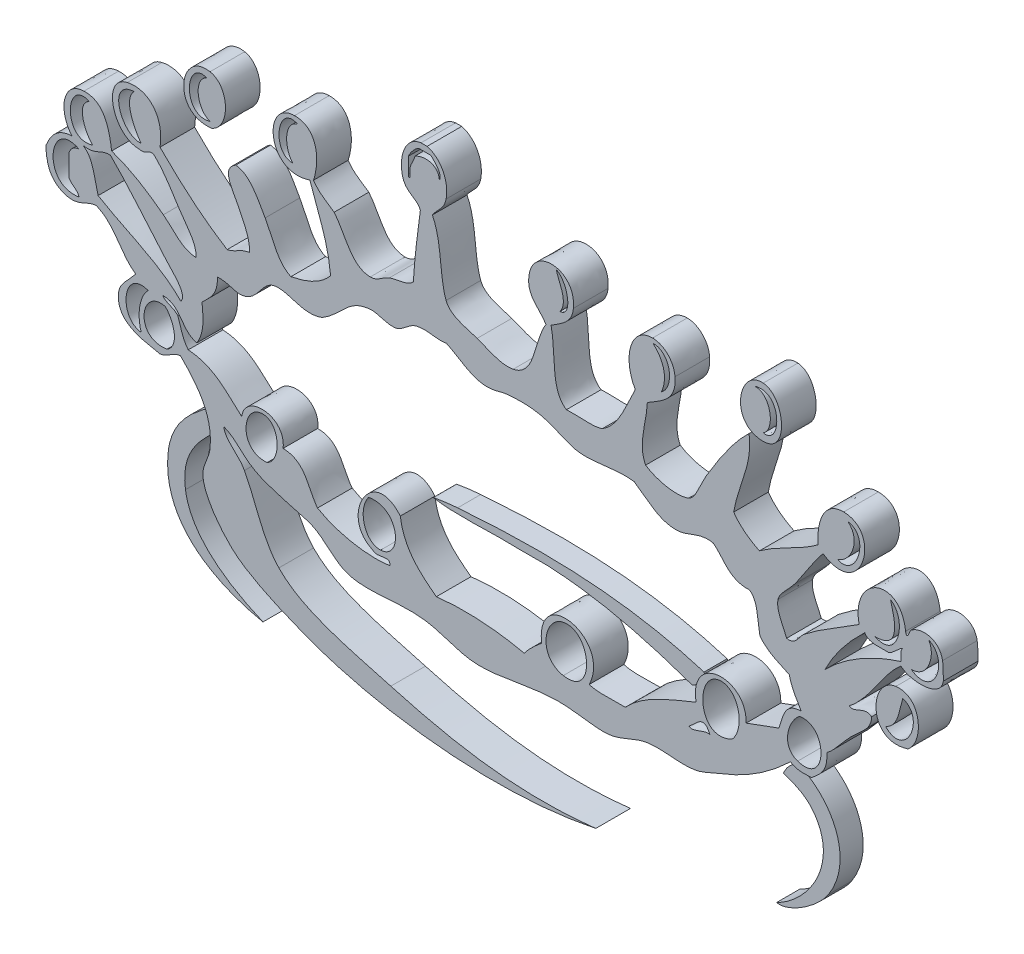
SolidWorks part; units mm, degrees
ref_plane "Front Plane" through (0, 0, 0) normal (0, 0, 1) x (1, 0, 0)
ref_plane "Top Plane" through (0, 0, 0) normal (0, 1, 0) x (1, 0, 0)
ref_plane "Right Plane" through (0, 0, 0) normal (1, 0, 0) x (0, 0, -1)
sketch "Sketch1" plane through (0, 0, 0) normal (0, 0, 1) x (1, 0, 0)
  line L1 (0, 0) -> (155.4725, 0) construction
  line L2 (0, 0) -> (0, 91.1172) construction
  line L3 (0, 91.1172) -> (155.4725, 91.1172) construction
  line L4 (155.4725, 0) -> (155.4725, 91.1172) construction
  point P5 (0, 0)
  point P6 (0, 0)
  spline B0 degree 3 poles (112.0338, 34.261) (112.3994, 33.3103) (111.1196, 31.738) (109.9496, 31.2992) knots 5 5 5 5 6 6 6 6
  spline B1 degree 3 poles (69.3629, 37.5518) (85.2319, 38.7584) (98.7608, 38.3196) (112.0338, 34.261) knots 4 4 4 4 5 5 5 5
  spline B2 degree 3 poles (65.1946, 36.9668) (64.6461, 37.0764) (69.1435, 37.5518) (69.3629, 37.5518) knots 3 3 3 3 4 4 4 4
  spline B3 degree 3 poles (79.8204, 36.6742) (75.1767, 36.8936) (69.6189, 36.2355) (65.1946, 36.9668) knots 2 2 2 2 3 3 3 3
  spline B4 degree 3 poles (84.9029, 36.6742) (83.2209, 36.7474) (81.5389, 36.6011) (79.8204, 36.6742) knots 1 1 1 1 2 2 2 2
  spline B5 degree 3 poles (109.9496, 31.2992) (102.7098, 33.8588) (94.4097, 36.2355) (84.9029, 36.6742) knots 0 0 0 0 1 1 1 1
  spline B6 degree 3 poles (149.3296, 42.3783) (142.1264, 40.1113) (142.5652, 50.0934) (147.2454, 50.715) knots 1 1 1 1 2 2 2 2
  spline B7 degree 3 poles (147.2454, 50.715) (151.7063, 51.3001) (152.2548, 44.7184) (149.3296, 42.3783) knots 0 0 0 0 1 1 1 1
  spline B8 degree 3 poles (145.4538, 43.8409) (149.0005, 40.2576) (152.5107, 48.1921) (148.4521, 49.5084) knots 1 1 1 1 2 2 2 2
  spline B9 degree 3 poles (148.4521, 49.5084) (147.8305, 47.2414) (147.5745, 44.6453) (145.4538, 43.8409) knots 0 0 0 0 1 1 1 1
  spline B10 degree 3 poles (28.7763, 75.1767) (21.7193, 74.3357) (23.0356, 84.5007) (28.4838, 83.5134) knots 1 1 1 1 2 2 2 2
  spline B11 degree 3 poles (28.4838, 83.5134) (31.8843, 82.8918) (32.1037, 76.6027) (28.7763, 75.1767) knots 0 0 0 0 1 1 1 1
  spline B12 degree 3 poles (27.8987, 82.3068) (24.1326, 83.7694) (23.511, 74.7379) (28.4838, 76.0543) knots 1 1 1 1 2 2 2 2
  spline B13 degree 3 poles (28.4838, 76.0543) (26.2899, 76.749) (25.4855, 81.1733) (27.8987, 82.3068) knots 0 0 0 0 1 1 1 1
  spline B14 degree 3 poles (123.4053, 76.0543) (118.396, 77.0049) (120.1511, 85.0491) (124.2829, 84.7201) knots 1 1 1 1 2 2 2 2
  spline B15 degree 3 poles (124.2829, 84.7201) (128.2684, 84.4275) (129.0363, 74.9939) (123.4053, 76.0543) knots 0 0 0 0 1 1 1 1
  spline B16 degree 3 poles (122.7837, 83.5134) (125.6358, 83.7328) (126.4402, 78.5772) (124.2829, 77.2609) knots 1 1 1 1 2 2 2 2
  spline B17 degree 3 poles (124.2829, 77.2609) (127.5371, 76.5296) (127.7199, 85.0126) (122.7837, 83.5134) knots 0 0 0 0 1 1 1 1
  spline B18 degree 3 poles (22.2312, 16.71) (21.4268, 22.0118) (24.4251, 25.2295) (27.6062, 28.045) knots 5 5 5 5 6 6 6 6
  spline B19 degree 3 poles (35.6504, 3.5833) (30.3851, 5.8138) (23.2185, 9.9455) (22.2312, 16.71) knots 4 4 4 4 5 5 5 5
  spline B20 degree 3 poles (19.2695, 21.1709) (17.905, 10.2892) (27.1415, 5.3254) (35.6504, 3.5833) knots 2 2 2 2 3 3 3 3
  spline B21 degree 3 poles (27.3137, 31.6283) (23.4744, 29.1419) (19.9642, 26.1436) (19.2695, 21.1709) knots 1 1 1 1 2 2 2 2
  spline B22 degree 3 poles (27.6062, 28.045) (27.7159, 29.471) (27.0577, 30.0926) (27.3137, 31.6283) knots 0 0 0 0 1 1 1 1
  spline B23 degree 3 poles (133.5703, 11.6641) (138.0677, 18.5382) (134.4844, 25.9243) (128.4512, 28.63) knots 5 5 5 5 6 6 6 6
  spline B24 degree 3 poles (124.612, 5.9966) (126.4402, 5.4481) (131.4861, 8.5195) (133.5703, 11.6641) knots 4 4 4 4 5 5 5 5
  spline B25 degree 3 poles (130.572, 23.2916) (135.8817, 17.1462) (130.2406, 8.7413) (124.612, 5.9966) knots 2 2 2 2 3 3 3 3
  spline B26 degree 3 poles (125.782, 25.9608) (127.8296, 25.3392) (129.4751, 24.4982) (130.572, 23.2916) knots 1 1 1 1 2 2 2 2
  spline B27 degree 3 poles (128.4512, 28.63) (127.1715, 28.1181) (126.2939, 27.204) (125.782, 25.9608) knots 0 0 0 0 1 1 1 1
  spline B28 degree 3 poles (155.4725, 55.613) (154.9971, 52.4685) (149.5124, 52.7976) (148.123, 54.2236) knots 96 96 96 96 97 97 97 97
  spline B29 degree 3 poles (155.3262, 58.6113) (155.4359, 58.2091) (155.4725, 56.6368) (155.4725, 55.613) knots 95 95 95 95 96 96 96 96
  spline B30 degree 3 poles (149.805, 60.403) (151.7429, 61.9753) (154.8874, 61.3537) (155.3262, 58.6113) knots 94 94 94 94 95 95 95 95
  spline B31 degree 3 poles (148.9274, 59.8179) (149.1468, 58.4285) (149.7318, 60.3298) (149.805, 60.403) knots 93 93 93 93 94 94 94 94
  spline B32 degree 3 poles (140.8832, 56.8197) (139.3841, 64.0594) (148.0499, 67.4234) (148.9274, 59.8179) knots 92 92 92 92 93 93 93 93
  spline B33 degree 3 poles (131.3399, 50.5671) (134.4478, 53.0535) (137.6655, 54.6623) (140.8832, 56.8197) knots 91 91 91 91 92 92 92 92
  spline B34 degree 3 poles (128.3416, 48.4829) (129.9138, 48.1173) (130.4623, 49.8724) (131.3399, 50.5671) knots 90 90 90 90 91 91 91 91
  spline B35 degree 3 poles (126.8424, 53.5654) (126.5133, 51.8103) (127.5737, 50.3843) (128.3416, 48.4829) knots 89 89 89 89 90 90 90 90
  spline B36 degree 3 poles (129.8407, 57.4413) (128.9632, 56.2346) (127.0984, 54.772) (126.8424, 53.5654) knots 88 88 88 88 89 89 89 89
  spline B37 degree 3 poles (134.6307, 64.3154) (133.2412, 62.7431) (131.6324, 59.9642) (129.8407, 57.4413) knots 87 87 87 87 88 88 88 88
  spline B38 degree 3 poles (138.214, 72.3596) (144.9784, 72.2499) (141.4682, 59.8911) (134.6307, 64.3154) knots 86 86 86 86 87 87 87 87
  spline B39 degree 3 poles (133.7531, 65.1929) (133.5337, 68.6666) (134.7404, 72.3962) (138.214, 72.3596) knots 85 85 85 85 86 86 86 86
  spline B40 degree 3 poles (123.6247, 59.2329) (126.6961, 61.5365) (130.6817, 62.8894) (133.7531, 65.1929) knots 84 84 84 84 85 85 85 85
  spline B41 degree 3 poles (119.1638, 62.8162) (120.2608, 61.244) (121.8331, 60.1105) (123.6247, 59.2329) knots 83 83 83 83 84 84 84 84
  spline B42 degree 3 poles (121.8331, 75.9429) (122.4912, 71.2261) (119.8586, 67.204) (119.1638, 62.8162) knots 82 82 82 82 83 83 83 83
  spline B43 degree 3 poles (114.3739, 65.8145) (116.6775, 69.7269) (119.237, 73.4931) (121.8331, 75.9429) knots 81 81 81 81 82 82 82 82
  spline B44 degree 3 poles (111.3756, 61.0246) (112.6919, 61.6096) (113.277, 63.9497) (114.3739, 65.8145) knots 80 80 80 80 81 81 81 81
  spline B45 degree 3 poles (103.9164, 62.2312) (105.9275, 60.8783) (109.4743, 60.1836) (111.3756, 61.0246) knots 79 79 79 79 80 80 80 80
  spline B46 degree 3 poles (104.2089, 71.7746) (104.1358, 68.63) (102.4904, 65.0467) (103.9164, 62.2312) knots 78 78 78 78 79 79 79 79
  spline B47 degree 3 poles (108.9989, 78.0271) (109.2914, 74.3706) (106.6588, 73.2737) (104.2089, 71.7746) knots 77 77 77 77 78 78 78 78
  spline B48 degree 3 poles (105.1231, 81.9029) (106.805, 81.9029) (108.7795, 80.5135) (108.9989, 78.0271) knots 76 76 76 76 77 77 77 77
  spline B49 degree 3 poles (102.1248, 72.6521) (99.9309, 76.4548) (101.1741, 81.8664) (105.1231, 81.9029) knots 75 75 75 75 76 76 76 76
  spline B50 degree 3 poles (96.4573, 63.9863) (99.3824, 65.8145) (100.4794, 69.5076) (102.1248, 72.6521) knots 74 74 74 74 75 75 75 75
  spline B51 degree 3 poles (90.2047, 63.6938) (92.2158, 63.8401) (94.9215, 63.3281) (96.4573, 63.9863) knots 73 73 73 73 74 74 74 74
  spline B52 degree 3 poles (87.5355, 75.0288) (88.4496, 71.2992) (87.3527, 65.4855) (90.2047, 63.6938) knots 72 72 72 72 73 73 73 73
  spline B53 degree 3 poles (91.4114, 79.4897) (91.192, 77.0399) (89.254, 76.1623) (87.5355, 75.0288) knots 71 71 71 71 72 72 72 72
  spline B54 degree 3 poles (86.658, 74.6997) (85.6342, 76.3817) (83.6597, 77.2227) (83.6597, 79.7822) (83.6597, 85.8519) (91.9598, 85.6691) (91.4114, 79.4897) knots 69 69 69 69 70 70 70 71 71 71 71
  spline B55 degree 3 poles (80.9905, 65.1564) (84.9394, 65.9242) (84.5738, 71.482) (86.658, 74.6997) knots 68 68 68 68 69 69 69 69
  spline B56 degree 3 poles (74.7379, 66.6555) (76.8221, 65.9242) (78.76, 64.7176) (80.9905, 65.1564) knots 67 67 67 67 68 68 68 68
  spline B57 degree 3 poles (69.3629, 69.6538) (70.0942, 67.7159) (72.9463, 67.2771) (74.7379, 66.6555) knots 66 66 66 66 67 67 67 67
  spline B58 degree 3 poles (66.9862, 81.2813) (68.7048, 77.9174) (68.1563, 72.8715) (69.3629, 69.6538) knots 65 65 65 65 66 66 66 66
  spline B59 degree 3 poles (69.3629, 84.8647) (69.0338, 83.0364) (67.7175, 82.488) (66.9862, 81.2813) knots 64 64 64 64 65 65 65 65
  spline B60 degree 3 poles (66.0721, 91.1172) (68.4854, 90.459) (69.8748, 87.7533) (69.3629, 84.8647) knots 63 63 63 63 64 64 64 64
  spline B61 degree 3 poles (65.0117, 91.1172) (65.1214, 91.1172) (65.1214, 91.1172) (65.1946, 91.1172) (65.4871, 91.1172) (65.7796, 91.1172) (66.0721, 91.1172) knots 61 61 61 61 62 62 62 63 63 63 63
  spline B62 degree 3 poles (61.9038, 84.2431) (61.0628, 86.8757) (62.0866, 90.715) (65.0117, 91.1172) knots 60 60 60 60 61 61 61 61
  spline B63 degree 3 poles (64.9021, 80.9523) (64.317, 82.4148) (62.5254, 82.3783) (61.9038, 84.2431) knots 59 59 59 59 60 60 60 60
  spline B64 degree 3 poles (63.6954, 69.6172) (63.9148, 73.5662) (64.4267, 77.2592) (64.9021, 80.9523) knots 58 58 58 58 59 59 59 59
  spline B65 degree 3 poles (59.5271, 68.1181) (60.9165, 68.6666) (62.6351, 68.4472) (63.6954, 69.6172) knots 57 57 57 57 58 58 58 58
  spline B66 degree 3 poles (56.2363, 66.619) (57.516, 66.5824) (58.2107, 67.6062) (59.5271, 68.1181) knots 56 56 56 56 57 57 57 57
  spline B67 degree 3 poles (49.9837, 73.2006) (51.9948, 70.7873) (52.8358, 66.6921) (56.2363, 66.619) knots 55 55 55 55 56 56 56 56
  spline B68 degree 3 poles (46.4004, 76.1989) (47.2779, 74.8825) (48.6674, 74.0781) (49.9837, 73.2006) knots 54 54 54 54 55 55 55 55
  spline B69 degree 3 poles (43.1096, 84.2431) (46.9123, 84.3162) (47.6436, 80.0381) (46.4004, 76.1989) knots 53 53 53 53 54 54 54 54
  spline B70 degree 3 poles (45.7788, 75.9064) (38.2099, 73.42) (37.4786, 84.1699) (43.1096, 84.2431) knots 52 52 52 52 53 53 53 53
  spline B71 degree 3 poles (49.3621, 63.3647) (48.9233, 68.3009) (47.0951, 71.8477) (45.7788, 75.9064) knots 51 51 51 51 52 52 52 52
  spline B72 degree 3 poles (42.488, 59.7814) (45.4131, 60.3299) (47.7898, 61.4268) (49.3621, 63.3647) knots 50 50 50 50 51 51 51 51
  spline B73 degree 3 poles (38.0271, 66.363) (39.38, 63.9863) (40.0747, 60.9149) (42.488, 59.7814) knots 49 49 49 49 50 50 50 50
  spline B74 degree 3 poles (32.9446, 71.738) (35.3579, 71.5186) (36.7108, 68.6666) (38.0271, 66.363) knots 48 48 48 48 49 49 49 49
  spline B75 degree 3 poles (33.2372, 66.0705) (32.4693, 67.7159) (30.312, 70.2388) (32.9446, 71.738) knots 47 47 47 47 48 48 48 48
  spline B76 degree 3 poles (35.3213, 59.8179) (35.431, 62.0849) (34.1513, 64.1326) (33.2372, 66.0705) knots 46 46 46 46 47 47 47 47
  spline B77 degree 3 poles (31.4455, 58.3188) (32.9446, 58.6113) (33.7125, 59.6351) (35.3213, 59.8179) knots 45 45 45 45 46 46 46 46
  spline B78 degree 3 poles (19.818, 67.8621) (23.3282, 64.3154) (27.0943, 61.0246) (31.4455, 58.3188) knots 44 44 44 44 45 45 45 45
  spline B79 degree 3 poles (14.1505, 74.7363) (17.5875, 75.5407) (20.5858, 72.8715) (19.818, 67.8621) knots 43 43 43 43 44 44 44 44
  spline B80 degree 3 poles (16.2347, 65.778) (11.6641, 65.7414) (9.5799, 73.6759) (14.1505, 74.7363) knots 42 42 42 42 43 43 43 43
  spline B81 degree 3 poles (18.9039, 66.0705) (17.9898, 66.8749) (17.5875, 65.4123) (16.2347, 65.778) knots 41 41 41 41 42 42 42 42
  spline B82 degree 3 poles (23.0722, 60.403) (21.7925, 62.414) (20.5127, 64.5348) (18.9039, 66.0705) knots 40 40 40 40 41 41 41 41
  spline B83 degree 3 poles (26.0705, 54.443) (26.1802, 56.6368) (24.2789, 58.5382) (23.0722, 60.403) knots 39 39 39 39 40 40 40 40
  spline B84 degree 3 poles (20.403, 58.0263) (22.085, 56.7831) (23.511, 54.5161) (26.0705, 54.443) knots 38 38 38 38 39 39 39 39
  spline B85 degree 3 poles (11.4447, 63.1088) (15.1012, 61.829) (17.7338, 60.0373) (20.403, 58.0263) knots 37 37 37 37 38 38 38 38
  spline B86 degree 3 poles (6.6547, 69.6904) (9.9456, 69.8001) (10.9694, 66.7652) (11.4447, 63.1088) knots 36 36 36 36 37 37 37 37
  spline B87 degree 3 poles (4.5706, 61.9387) (2.1207, 64.7907) (2.9983, 69.5807) (6.6547, 69.6904) knots 35 35 35 35 36 36 36 36
  spline B88 degree 3 poles (0.1097, 58.3554) (0.8775, 60.2567) (2.0476, 61.7924) (4.5706, 61.9387) knots 34 34 34 34 35 35 35 35
  spline B89 degree 3 poles (0.2925, 56.2712) (0.2194, 56.4175) (0, 57.6241) (0.1097, 58.3554) knots 33 33 33 33 34 34 34 34
  spline B90 degree 3 poles (4.2781, 52.3954) (2.1939, 52.5782) (0.585, 54.1505) (0.2925, 56.2712) knots 32 32 32 32 33 33 33 33
  spline B91 degree 3 poles (8.7389, 53.602) (7.0935, 53.4192) (6.0332, 52.2491) (4.2781, 52.3954) knots 31 31 31 31 32 32 32 32
  spline B92 degree 3 poles (15.6131, 46.7278) (12.9073, 48.5926) (12.0297, 52.3222) (8.7389, 53.602) knots 30 30 30 30 31 31 31 31
  spline B93 degree 3 poles (12.6148, 41.6454) (12.4685, 44.0221) (14.187, 44.8265) (15.6131, 46.7278) knots 29 29 29 29 30 30 30 30
  spline B94 degree 3 poles (19.7814, 36.8554) (16.3444, 37.5136) (12.7976, 38.1717) (12.6148, 41.6454) knots 28 28 28 28 29 29 29 29
  spline B95 degree 3 poles (23.3647, 38.3546) (21.829, 38.2083) (21.3171, 37.0382) (19.7814, 36.8554) knots 27 27 27 27 28 28 28 28
  spline B96 degree 3 poles (28.4472, 26.727) (29.1054, 31.7729) (26.5824, 35.1735) (23.3647, 38.3546) knots 26 26 26 26 27 27 27 27
  spline B97 degree 3 poles (27.2406, 22.5587) (27.2406, 24.0578) (28.2278, 25.301) (28.4472, 26.727) knots 25 25 25 25 26 26 26 26
  spline B98 degree 3 poles (32.3231, 13.8929) (30.0926, 15.9771) (27.2772, 19.7066) (27.2406, 22.5587) knots 24 24 24 24 25 25 25 25
  spline B99 degree 3 poles (44.8647, 7.3113) (40.2576, 9.1029) (35.1385, 11.2968) (32.3231, 13.8929) knots 23 23 23 23 24 24 24 24
  spline B100 degree 3 poles (95.2872, 3.4354) (78.5772, -0.0748) (58.5398, 2.046) (44.8647, 7.3113) knots 22 22 22 22 23 23 23 23
  spline B101 degree 3 poles (59.783, 7.0187) (70.0942, 4.1301) (81.1733, 1.8266) (95.2872, 3.4354) knots 21 21 21 21 22 22 22 22
  spline B102 degree 3 poles (40.4038, 15.0629) (44.4625, 10.858) (52.0314, 9.176) (59.783, 7.0187) knots 20 20 20 20 21 21 21 21
  spline B103 degree 3 poles (34.4438, 26.6905) (36.4549, 22.9974) (37.4421, 18.1709) (40.4038, 15.0629) knots 19 19 19 19 20 20 20 20
  spline B104 degree 3 poles (30.8605, 31.4804) (31.0799, 29.6156) (33.3469, 28.7015) (34.4438, 26.6905) knots 18 18 18 18 19 19 19 19
  spline B105 degree 3 poles (36.2355, 27.6046) (34.0416, 28.8112) (33.0544, 30.676) (30.8605, 31.4804) knots 17 17 17 17 18 18 18 18
  spline B106 degree 3 poles (41.0254, 25.8129) (39.2703, 26.398) (37.8077, 26.727) (36.2355, 27.6046) knots 16 16 16 16 17 17 17 17
  spline B107 degree 3 poles (46.1079, 24.3138) (44.5722, 24.9719) (42.5977, 25.2645) (41.0254, 25.8129) knots 15 15 15 15 16 16 16 16
  spline B108 degree 3 poles (52.3604, 20.1454) (49.9837, 20.9133) (48.3749, 23.3631) (46.1079, 24.3138) knots 14 14 14 14 15 15 15 15
  spline B109 degree 3 poles (65.7796, 19.8529) (60.9897, 20.5111) (55.9072, 18.9754) (52.3604, 20.1454) knots 13 13 13 13 14 14 14 14
  spline B110 degree 3 poles (74.7379, 17.7687) (71.4471, 17.8784) (68.7048, 19.4507) (65.7796, 19.8529) knots 12 12 12 12 13 13 13 13
  spline B111 degree 3 poles (88.4496, 19.2679) (83.8425, 19.1947) (78.9063, 17.6225) (74.7379, 17.7687) knots 11 11 11 11 12 12 12 12
  spline B112 degree 3 poles (97.7005, 18.6828) (95.0313, 18.3172) (91.8867, 19.341) (88.4496, 19.2679) knots 10 10 10 10 11 11 11 11
  spline B113 degree 3 poles (104.2821, 20.767) (102.0882, 20.4745) (99.9675, 18.9754) (97.7005, 18.6828) knots 9 9 9 9 10 10 10 10
  spline B114 degree 3 poles (112.3263, 20.767) (109.7668, 20.3648) (106.9513, 21.1327) (104.2821, 20.767) knots 8 8 8 8 9 9 9 9
  spline B115 degree 3 poles (117.1163, 22.5587) (115.544, 21.9736) (113.9717, 21.023) (112.3263, 20.767) knots 7 7 7 7 8 8 8 8
  spline B116 degree 3 poles (129.0363, 30.3104) (125.8552, 27.2755) (122.089, 24.46) (117.1163, 22.5587) knots 6 6 6 6 7 7 7 7
  spline B117 degree 3 poles (132.6196, 29.7253) (131.157, 29.6522) (129.7676, 29.6522) (129.0363, 30.3104) knots 5 5 5 5 6 6 6 6
  spline B118 degree 3 poles (135.2888, 34.8078) (135.5082, 31.9923) (134.0456, 30.8954) (132.6196, 29.7253) knots 4 4 4 4 5 5 5 5
  spline B119 degree 3 poles (139.4572, 39.2687) (137.9946, 37.8061) (136.8245, 35.9413) (135.2888, 34.8078) knots 3 3 3 3 4 4 4 4
  spline B120 degree 3 poles (143.0405, 44.0586) (143.0771, 42.011) (140.8832, 40.7312) (139.4572, 39.2687) knots 2 2 2 2 3 3 3 3
  spline B121 degree 3 poles (139.1647, 43.7661) (140.0422, 42.9982) (141.8339, 45.119) (143.0405, 44.0586) knots 1 1 1 1 2 2 2 2
  spline B122 degree 3 poles (148.123, 54.2236) (144.7225, 51.2984) (142.8942, 46.6181) (139.1647, 43.7661) knots 0 0 0 0 1 1 1 1
  spline B123 degree 3 poles (90.5338, 31.5918) (86.4386, 31.9208) (84.7932, 24.4617) (89.6563, 23.5476) knots 1 1 1 1 2 2 2 2
  spline B124 degree 3 poles (89.6563, 23.5476) (95.1044, 22.5603) (94.6656, 31.2992) (90.5338, 31.5918) knots 0 0 0 0 1 1 1 1
  spline B125 degree 3 poles (85.8901, 26.5093) (84.9029, 35.9429) (98.1392, 32.835) (94.1537, 24.4617) knots 36 36 36 36 37 37 37 37
  spline B126 degree 3 poles (82.8918, 23.511) (83.7328, 24.6811) (84.7932, 25.5586) (85.8901, 26.5093) knots 35 35 35 35 36 36 36 36
  spline B127 degree 3 poles (67.681, 24.3885) (73.056, 25.0101) (78.3944, 24.5348) (82.8918, 23.511) knots 34 34 34 34 35 35 35 35
  spline B128 degree 3 poles (61.4284, 33.3469) (62.05, 28.886) (64.7558, 26.5458) (67.681, 24.3885) knots 33 33 33 33 34 34 34 34
  spline B129 degree 3 poles (56.6385, 25.8877) (50.6785, 28.5569) (56.6019, 39.1606) (61.4284, 33.3469) knots 32 32 32 32 33 33 33 33
  spline B130 degree 3 poles (59.6368, 25.0101) (59.7465, 26.6555) (57.6623, 24.9736) (56.6385, 25.8877) knots 31 31 31 31 32 32 32 32
  spline B131 degree 3 poles (47.0951, 27.3868) (50.0934, 25.6317) (55.1759, 24.352) (59.6368, 25.0101) knots 30 30 30 30 31 31 31 31
  spline B132 degree 3 poles (41.1351, 33.3469) (45.0475, 33.2737) (45.3766, 29.6173) (47.0951, 27.3868) knots 29 29 29 29 30 30 30 30
  spline B133 degree 3 poles (33.9684, 34.5535) (34.5535, 38.7584) (41.7201, 38.2831) (41.1351, 33.3469) knots 28 28 28 28 29 29 29 29
  spline B134 degree 3 poles (24.7176, 39.9285) (29.2882, 39.5994) (31.3358, 36.7839) (33.9684, 34.5535) knots 27 27 27 27 28 28 28 28
  spline B135 degree 3 poles (22.926, 44.0968) (23.4379, 42.6343) (23.7669, 40.9889) (24.7176, 39.9285) knots 26 26 26 26 27 27 27 27
  spline B136 degree 3 poles (20.2567, 45.8885) (20.8783, 45.011) (22.3044, 44.9744) (22.926, 44.0968) knots 25 25 25 25 26 26 26 26
  spline B137 degree 3 poles (26.2168, 41.7201) (23.4013, 42.3052) (23.6207, 45.8885) (20.2567, 45.8885) knots 24 24 24 24 25 25 25 25
  spline B138 degree 3 poles (27.0943, 48.3018) (27.46, 45.6325) (27.3503, 43.5484) (26.2168, 41.7201) knots 23 23 23 23 24 24 24 24
  spline B139 degree 3 poles (29.7635, 53.3842) (29.8732, 50.6785) (28.4106, 49.545) (27.0943, 48.3018) knots 22 22 22 22 23 23 23 23
  spline B140 degree 3 poles (34.2244, 52.7992) (32.6521, 52.5067) (32.1402, 53.4208) (29.7635, 53.3842) knots 21 21 21 21 22 22 22 22
  spline B141 degree 3 poles (39.5994, 56.9676) (37.4421, 56.5653) (36.8205, 53.2745) (34.2244, 52.7992) knots 20 20 20 20 21 21 21 21
  spline B142 degree 3 poles (47.9361, 56.3825) (44.4259, 55.0296) (42.1955, 57.4795) (39.5994, 56.9676) knots 19 19 19 19 20 20 20 20
  spline B143 degree 3 poles (56.2728, 61.7575) (52.3239, 61.5016) (51.2635, 58.3204) (47.9361, 56.3825) knots 18 18 18 18 19 19 19 19
  spline B144 degree 3 poles (60.7337, 61.1725) (59.0517, 60.88) (57.6623, 61.8672) (56.2728, 61.7575) knots 17 17 17 17 18 18 18 18
  spline B145 degree 3 poles (64.317, 63.2567) (62.8544, 62.9276) (61.8672, 61.3919) (60.7337, 61.1725) knots 16 16 16 16 17 17 17 17
  spline B146 degree 3 poles (69.3995, 63.2567) (67.4981, 62.9276) (66.2184, 63.6954) (64.317, 63.2567) knots 15 15 15 15 16 16 16 16
  spline B147 degree 3 poles (76.2736, 60.2584) (73.4582, 60.3681) (71.5934, 62.306) (69.3995, 63.2567) knots 14 14 14 14 15 15 15 15
  spline B148 degree 3 poles (79.857, 60.8434) (78.76, 60.7337) (77.6997, 60.1852) (76.2736, 60.2584) knots 13 13 13 13 14 14 14 14
  spline B149 degree 3 poles (90.8995, 58.7592) (87.1333, 60.2218) (85.6342, 61.3919) (79.857, 60.8434) knots 12 12 12 12 13 13 13 13
  spline B150 degree 3 poles (101.942, 58.7592) (98.2124, 59.3077) (93.8977, 57.5892) (90.8995, 58.7592) knots 11 11 11 11 12 12 12 12
  spline B151 degree 3 poles (109.4011, 55.1759) (106.1469, 55.0662) (104.3186, 57.2235) (101.942, 58.7592) knots 10 10 10 10 11 11 11 11
  spline B152 degree 3 poles (115.6537, 56.3825) (113.2038, 56.931) (111.4487, 55.249) (109.4011, 55.1759) knots 9 9 9 9 10 10 10 10
  spline B153 degree 3 poles (121.9062, 52.5067) (118.3594, 52.3239) (117.555, 54.8834) (115.6537, 56.3825) knots 8 8 8 8 9 9 9 9
  spline B154 degree 3 poles (123.6979, 46.5467) (123.2591, 48.6674) (123.4419, 51.4463) (121.9062, 52.5067) knots 7 7 7 7 8 8 8 8
  spline B155 degree 3 poles (128.7803, 43.2558) (126.8424, 44.1334) (124.8679, 44.9013) (123.6979, 46.5467) knots 6 6 6 6 7 7 7 7
  spline B156 degree 3 poles (130.8645, 38.795) (130.0601, 40.1844) (129.1825, 41.5007) (128.7803, 43.2558) knots 5 5 5 5 6 6 6 6
  spline B157 degree 3 poles (126.9887, 34.3341) (127.6468, 36.4548) (128.049, 38.8315) (130.8645, 38.795) knots 4 4 4 4 5 5 5 5
  spline B158 degree 3 poles (121.3212, 32.2499) (123.2225, 32.9081) (125.0508, 33.6759) (126.9887, 34.3341) knots 3 3 3 3 4 4 4 4
  spline B159 degree 3 poles (112.6554, 31.0433) (111.339, 38.5025) (121.4674, 39.0509) (121.3212, 32.2499) knots 2 2 2 2 3 3 3 3
  spline B160 degree 3 poles (100.4062, 24.1692) (103.4411, 27.4965) (108.1214, 29.1785) (112.6554, 31.0433) knots 1 1 1 1 2 2 2 2
  spline B161 degree 3 poles (94.1537, 24.4617) (95.7625, 23.8766) (98.3586, 24.2788) (100.4062, 24.1692) knots 0 0 0 0 1 1 1 1
  spline B162 degree 3 poles (58.0279, 26.5458) (61.8672, 26.6921) (61.5747, 34.3341) (55.9437, 33.42) knots 1 1 1 1 2 2 2 2
  spline B163 degree 3 poles (55.9437, 33.42) (54.0424, 30.897) (55.1759, 26.4362) (58.0279, 26.5458) knots 0 0 0 0 1 1 1 1
  spline B164 degree 3 poles (115.032, 27.4234) (113.9351, 29.9098) (112.765, 27.8987) (111.4487, 26.8384) knots 1 1 1 1 2 2 2 2
  spline B165 degree 3 poles (111.4487, 26.8384) (112.2531, 26.2533) (113.6792, 27.5697) (115.032, 27.4234) knots 0 0 0 0 1 1 1 1
  spline B166 degree 3 poles (117.1162, 36.3817) (112.3263, 36.4914) (112.6188, 25.4855) (118.9079, 28.63) knots 1 1 1 1 2 2 2 2
  spline B167 degree 3 poles (118.9079, 28.63) (121.1018, 31.0799) (120.1877, 36.1989) (117.1162, 36.3817) knots 0 0 0 0 1 1 1 1
  spline B168 degree 3 poles (38.0637, 36.7108) (34.1147, 37.4055) (33.0178, 29.471) (38.3562, 29.8367) knots 1 1 1 1 2 2 2 2
  spline B169 degree 3 poles (38.3562, 29.8367) (40.8426, 31.1164) (40.6232, 36.2355) (38.0637, 36.7108) knots 0 0 0 0 1 1 1 1
  spline B170 degree 3 poles (130.5354, 37.8809) (128.4878, 36.1989) (127.3177, 31.994) (130.2429, 31.0067) knots 1 1 1 1 2 2 2 2
  spline B171 degree 3 poles (130.2429, 31.0067) (135.4716, 29.2516) (135.691, 38.7219) (130.5354, 37.8809) knots 0 0 0 0 1 1 1 1
  spline B172 degree 3 poles (20.7321, 44.4259) (16.3443, 45.5229) (15.2474, 37.2958) (21.0246, 38.1734) knots 1 1 1 1 2 2 2 2
  spline B173 degree 3 poles (21.0246, 38.1734) (23.255, 39.4897) (22.2312, 42.9999) (20.7321, 44.4259) knots 0 0 0 0 1 1 1 1
  spline B174 degree 3 poles (17.7703, 45.34) (13.3095, 47.022) (12.5416, 38.9047) (16.5637, 38.4659) knots 1 1 1 1 2 2 2 2
  spline B175 degree 3 poles (16.5637, 38.4659) (15.9421, 40.3673) (16.0153, 43.5849) (17.7703, 45.34) knots 0 0 0 0 1 1 1 1
  spline B176 degree 3 poles (9.1045, 55.249) (13.9311, 52.3239) (19.7083, 50.4591) (23.4379, 46.5467) knots 4 4 4 4 5 5 5 5
  spline B177 degree 3 poles (6.4353, 61.5016) (8.3367, 60.4046) (8.4098, 57.516) (9.1045, 55.249) knots 3 3 3 3 4 4 4 4
  spline B178 degree 3 poles (11.2253, 62.3791) (9.3239, 62.4157) (8.7755, 61.0262) (6.4353, 61.5016) knots 2 2 2 2 3 3 3 3
  spline B179 degree 3 poles (20.7686, 51.6291) (17.7338, 55.0662) (14.187, 59.4905) (11.2253, 62.3791) knots 1 1 1 1 2 2 2 2
  spline B180 degree 3 poles (23.4379, 46.5467) (24.5348, 48.0824) (22.1581, 50.0203) (20.7686, 51.6291) knots 0 0 0 0 1 1 1 1
  spline B181 degree 3 poles (146.0388, 55.1759) (144.3934, 55.2125) (142.4189, 54.9199) (141.8704, 56.09) knots 4 4 4 4 5 5 5 5
  spline B182 degree 3 poles (148.4155, 56.9676) (148.0864, 57.0772) (146.9163, 55.505) (146.0388, 55.1759) knots 3 3 3 3 4 4 4 4
  spline B183 degree 3 poles (148.123, 54.8834) (148.123, 55.6878) (148.0133, 56.6019) (148.4155, 56.9676) knots 2 2 2 2 3 3 3 3
  spline B184 degree 3 poles (134.9963, 47.1317) (138.4699, 50.6419) (142.8211, 53.2014) (148.123, 54.8834) knots 1 1 1 1 2 2 2 2
  spline B185 degree 3 poles (141.8704, 56.09) (139.1647, 53.5305) (136.7514, 50.6785) (134.9963, 47.1317) knots 0 0 0 0 1 1 1 1
  spline B186 degree 3 poles (5.8137, 60.5509) (0.4022, 63.2932) (-0.7679, 52.2873) (5.8137, 53.3842) knots 3 3 3 3 4 4 4 4
  spline B187 degree 3 poles (4.0221, 59.0517) (4.3146, 59.8562) (4.7534, 60.4778) (5.8137, 60.5509) knots 2 2 2 2 3 3 3 3
  spline B188 degree 3 poles (4.0221, 55.4684) (4.0221, 56.675) (4.0221, 57.8451) (4.0221, 59.0517) knots 1 1 1 1 2 2 2 2
  spline B189 degree 3 poles (5.8137, 53.3842) (5.4847, 54.3715) (4.4243, 54.5909) (4.0221, 55.4684) knots 0 0 0 0 1 1 1 1
  spline B190 degree 3 poles (152.9129, 60.5509) (154.1196, 58.8689) (153.0226, 54.6274) (149.9146, 54.5909) knots 1 1 1 1 2 2 2 2
  spline B191 degree 3 poles (149.9146, 54.5909) (153.9733, 51.7388) (156.5694, 58.9786) (152.9129, 60.5509) knots 0 0 0 0 1 1 1 1
  spline B192 degree 3 poles (146.3313, 63.2567) (146.9163, 61.1359) (148.4521, 56.346) (143.6621, 56.3825) knots 1 1 1 1 2 2 2 2
  spline B193 degree 3 poles (143.6621, 56.3825) (147.8305, 54.408) (149.2199, 61.5747) (146.3313, 63.2567) knots 0 0 0 0 1 1 1 1
  spline B194 degree 3 poles (7.6054, 68.5951) (3.2542, 70.4964) (2.9251, 60.6971) (8.1904, 62.3425) knots 1 1 1 1 2 2 2 2
  spline B195 degree 3 poles (8.1904, 62.3425) (6.9107, 63.3664) (5.1556, 67.4616) (7.6054, 68.5951) knots 0 0 0 0 1 1 1 1
  spline B196 degree 3 poles (138.9087, 71.3009) (141.322, 69.3995) (139.4572, 65.3408) (137.117, 64.7192) knots 1 1 1 1 2 2 2 2
  spline B197 degree 3 poles (137.117, 64.7192) (140.5175, 63.0738) (142.9308, 70.7158) (138.9087, 71.3009) knots 0 0 0 0 1 1 1 1
  spline B198 degree 3 poles (15.3571, 73.9701) (10.494, 73.7507) (13.0535, 66.4743) (16.5637, 66.8034) knots 1 1 1 1 2 2 2 2
  spline B199 degree 3 poles (16.5637, 66.8034) (15.6496, 67.9004) (13.3095, 72.0322) (15.3571, 73.9701) knots 0 0 0 0 1 1 1 1
  spline B200 degree 3 poles (105.1596, 81.1733) (106.8416, 79.7107) (107.8654, 77.334) (106.6588, 74.5917) knots 1 1 1 1 2 2 2 2
  spline B201 degree 3 poles (106.6588, 74.5917) (108.8892, 76.1274) (108.487, 81.1367) (105.1596, 81.1733) knots 0 0 0 0 1 1 1 1
  spline B202 degree 3 poles (43.6946, 83.2209) (40.0382, 84.976) (39.0509, 76.9318) (42.8171, 76.9684) knots 1 1 1 1 2 2 2 2
  spline B203 degree 3 poles (42.8171, 76.9684) (41.3179, 78.5406) (41.2082, 82.6724) (43.6946, 83.2209) knots 0 0 0 0 1 1 1 1
  spline B204 degree 3 poles (88.4862, 83.8059) (88.5228, 82.7456) (90.6801, 79.8935) (89.0712, 77.8459) knots 1 1 1 1 2 2 2 2
  spline B205 degree 3 poles (89.0712, 77.8459) (91.4479, 77.9922) (90.3876, 82.965) (88.4862, 83.8059) knots 0 0 0 0 1 1 1 1
  spline B206 degree 3 poles (63.9879, 88.6325) (65.6699, 89.51) (68.0466, 89.2906) (68.1929, 87.0967) knots 6 6 6 6 7 7 7 7
  spline B207 degree 3 poles (63.1104, 85.3417) (62.891, 86.9505) (63.732, 87.499) (63.9879, 88.6325) knots 5 5 5 5 6 6 6 6
  spline B208 degree 3 poles (62.8179, 85.3417) (62.7813, 84.6104) (63.1835, 84.8297) (63.1104, 85.3417) knots 4 4 4 4 5 5 5 5
  spline B209 degree 3 poles (62.8179, 88.0109) (62.8179, 87.1333) (62.8179, 86.2192) (62.8179, 85.3417) knots 3 3 3 3 4 4 4 4
  spline B210 degree 3 poles (64.6095, 90.095) (63.7686, 89.6197) (63.1104, 88.6325) (62.8179, 88.0109) knots 2 2 2 2 3 3 3 3
  spline B211 degree 3 poles (66.6937, 90.095) (65.999, 90.095) (65.3043, 90.095) (64.6095, 90.095) knots 1 1 1 1 2 2 2 2
  spline B212 degree 3 poles (68.1929, 87.0967) (68.8145, 88.0109) (67.425, 89.51) (66.6937, 90.095) knots 0 0 0 0 1 1 1 1
  spline B213 degree 3 poles (112.0338, 34.261) (112.3994, 33.3103) (111.1196, 31.738) (109.9496, 31.2992) knots 5 5 5 5 6 6 6 6
  spline B214 degree 3 poles (69.3629, 37.5518) (85.2319, 38.7584) (98.7608, 38.3196) (112.0338, 34.261) knots 4 4 4 4 5 5 5 5
  spline B215 degree 3 poles (65.1946, 36.9668) (64.6461, 37.0764) (69.1435, 37.5518) (69.3629, 37.5518) knots 3 3 3 3 4 4 4 4
  spline B216 degree 3 poles (79.8204, 36.6742) (75.1767, 36.8936) (69.6189, 36.2355) (65.1946, 36.9668) knots 2 2 2 2 3 3 3 3
  spline B217 degree 3 poles (84.9029, 36.6742) (83.2209, 36.7474) (81.5389, 36.6011) (79.8204, 36.6742) knots 1 1 1 1 2 2 2 2
  spline B218 degree 3 poles (109.9496, 31.2992) (102.7098, 33.8588) (94.4097, 36.2355) (84.9029, 36.6742) knots 0 0 0 0 1 1 1 1
  spline B219 degree 3 poles (149.3296, 42.3783) (142.1264, 40.1113) (142.5652, 50.0934) (147.2454, 50.715) knots 1 1 1 1 2 2 2 2
  spline B220 degree 3 poles (147.2454, 50.715) (151.7063, 51.3001) (152.2548, 44.7184) (149.3296, 42.3783) knots 0 0 0 0 1 1 1 1
  spline B221 degree 3 poles (145.4538, 43.8409) (149.0005, 40.2576) (152.5107, 48.1921) (148.4521, 49.5084) knots 1 1 1 1 2 2 2 2
  spline B222 degree 3 poles (148.4521, 49.5084) (147.8305, 47.2414) (147.5745, 44.6453) (145.4538, 43.8409) knots 0 0 0 0 1 1 1 1
  spline B223 degree 3 poles (28.7763, 75.1767) (21.7193, 74.3357) (23.0356, 84.5007) (28.4838, 83.5134) knots 1 1 1 1 2 2 2 2
  spline B224 degree 3 poles (28.4838, 83.5134) (31.8843, 82.8918) (32.1037, 76.6027) (28.7763, 75.1767) knots 0 0 0 0 1 1 1 1
  spline B225 degree 3 poles (27.8987, 82.3068) (24.1326, 83.7694) (23.511, 74.7379) (28.4838, 76.0543) knots 1 1 1 1 2 2 2 2
  spline B226 degree 3 poles (28.4838, 76.0543) (26.2899, 76.749) (25.4855, 81.1733) (27.8987, 82.3068) knots 0 0 0 0 1 1 1 1
  spline B227 degree 3 poles (123.4053, 76.0543) (118.396, 77.0049) (120.1511, 85.0491) (124.2829, 84.7201) knots 1 1 1 1 2 2 2 2
  spline B228 degree 3 poles (124.2829, 84.7201) (128.2684, 84.4275) (129.0363, 74.9939) (123.4053, 76.0543) knots 0 0 0 0 1 1 1 1
  spline B229 degree 3 poles (122.7837, 83.5134) (125.6358, 83.7328) (126.4402, 78.5772) (124.2829, 77.2609) knots 1 1 1 1 2 2 2 2
  spline B230 degree 3 poles (124.2829, 77.2609) (127.5371, 76.5296) (127.7199, 85.0126) (122.7837, 83.5134) knots 0 0 0 0 1 1 1 1
  spline B231 degree 3 poles (22.2312, 16.71) (21.4268, 22.0118) (24.4251, 25.2295) (27.6062, 28.045) knots 5 5 5 5 6 6 6 6
  spline B232 degree 3 poles (35.6504, 3.5833) (30.3851, 5.8138) (23.2185, 9.9455) (22.2312, 16.71) knots 4 4 4 4 5 5 5 5
  spline B233 degree 3 poles (19.2695, 21.1709) (17.905, 10.2892) (27.1415, 5.3254) (35.6504, 3.5833) knots 2 2 2 2 3 3 3 3
  spline B234 degree 3 poles (27.3137, 31.6283) (23.4744, 29.1419) (19.9642, 26.1436) (19.2695, 21.1709) knots 1 1 1 1 2 2 2 2
  spline B235 degree 3 poles (27.6062, 28.045) (27.7159, 29.471) (27.0577, 30.0926) (27.3137, 31.6283) knots 0 0 0 0 1 1 1 1
  spline B236 degree 3 poles (133.5703, 11.6641) (138.0677, 18.5382) (134.4844, 25.9243) (128.4512, 28.63) knots 5 5 5 5 6 6 6 6
  spline B237 degree 3 poles (124.612, 5.9966) (126.4402, 5.4481) (131.4861, 8.5195) (133.5703, 11.6641) knots 4 4 4 4 5 5 5 5
  spline B238 degree 3 poles (130.572, 23.2916) (135.8817, 17.1462) (130.2406, 8.7413) (124.612, 5.9966) knots 2 2 2 2 3 3 3 3
  spline B239 degree 3 poles (125.782, 25.9608) (127.8296, 25.3392) (129.4751, 24.4982) (130.572, 23.2916) knots 1 1 1 1 2 2 2 2
  spline B240 degree 3 poles (128.4512, 28.63) (127.1715, 28.1181) (126.2939, 27.204) (125.782, 25.9608) knots 0 0 0 0 1 1 1 1
  spline B241 degree 3 poles (90.5338, 31.5918) (86.4386, 31.9208) (84.7932, 24.4617) (89.6563, 23.5476) knots 1 1 1 1 2 2 2 2
  spline B242 degree 3 poles (89.6563, 23.5476) (95.1044, 22.5603) (94.6656, 31.2992) (90.5338, 31.5918) knots 0 0 0 0 1 1 1 1
  spline B243 degree 3 poles (85.8901, 26.5093) (84.9029, 35.9429) (98.1392, 32.835) (94.1537, 24.4617) knots 36 36 36 36 37 37 37 37
  spline B244 degree 3 poles (82.8918, 23.511) (83.7328, 24.6811) (84.7932, 25.5586) (85.8901, 26.5093) knots 35 35 35 35 36 36 36 36
  spline B245 degree 3 poles (67.681, 24.3885) (73.056, 25.0101) (78.3944, 24.5348) (82.8918, 23.511) knots 34 34 34 34 35 35 35 35
  spline B246 degree 3 poles (61.4284, 33.3469) (62.05, 28.886) (64.7558, 26.5458) (67.681, 24.3885) knots 33 33 33 33 34 34 34 34
  spline B247 degree 3 poles (56.6385, 25.8877) (50.6785, 28.5569) (56.6019, 39.1606) (61.4284, 33.3469) knots 32 32 32 32 33 33 33 33
  spline B248 degree 3 poles (59.6368, 25.0101) (59.7465, 26.6555) (57.6623, 24.9736) (56.6385, 25.8877) knots 31 31 31 31 32 32 32 32
  spline B249 degree 3 poles (47.0951, 27.3868) (50.0934, 25.6317) (55.1759, 24.352) (59.6368, 25.0101) knots 30 30 30 30 31 31 31 31
  spline B250 degree 3 poles (41.1351, 33.3469) (45.0475, 33.2737) (45.3766, 29.6173) (47.0951, 27.3868) knots 29 29 29 29 30 30 30 30
  spline B251 degree 3 poles (33.9684, 34.5535) (34.5535, 38.7584) (41.7201, 38.2831) (41.1351, 33.3469) knots 28 28 28 28 29 29 29 29
  spline B252 degree 3 poles (24.7176, 39.9285) (29.2882, 39.5994) (31.3358, 36.7839) (33.9684, 34.5535) knots 27 27 27 27 28 28 28 28
  spline B253 degree 3 poles (22.926, 44.0968) (23.4379, 42.6343) (23.7669, 40.9889) (24.7176, 39.9285) knots 26 26 26 26 27 27 27 27
  spline B254 degree 3 poles (20.2567, 45.8885) (20.8783, 45.011) (22.3044, 44.9744) (22.926, 44.0968) knots 25 25 25 25 26 26 26 26
  spline B255 degree 3 poles (26.2168, 41.7201) (23.4013, 42.3052) (23.6207, 45.8885) (20.2567, 45.8885) knots 24 24 24 24 25 25 25 25
  spline B256 degree 3 poles (27.0943, 48.3018) (27.46, 45.6325) (27.3503, 43.5484) (26.2168, 41.7201) knots 23 23 23 23 24 24 24 24
  spline B257 degree 3 poles (29.7635, 53.3842) (29.8732, 50.6785) (28.4106, 49.545) (27.0943, 48.3018) knots 22 22 22 22 23 23 23 23
  spline B258 degree 3 poles (34.2244, 52.7992) (32.6521, 52.5067) (32.1402, 53.4208) (29.7635, 53.3842) knots 21 21 21 21 22 22 22 22
  spline B259 degree 3 poles (39.5994, 56.9676) (37.4421, 56.5653) (36.8205, 53.2745) (34.2244, 52.7992) knots 20 20 20 20 21 21 21 21
  spline B260 degree 3 poles (47.9361, 56.3825) (44.4259, 55.0296) (42.1955, 57.4795) (39.5994, 56.9676) knots 19 19 19 19 20 20 20 20
  spline B261 degree 3 poles (56.2728, 61.7575) (52.3239, 61.5016) (51.2635, 58.3204) (47.9361, 56.3825) knots 18 18 18 18 19 19 19 19
  spline B262 degree 3 poles (60.7337, 61.1725) (59.0517, 60.88) (57.6623, 61.8672) (56.2728, 61.7575) knots 17 17 17 17 18 18 18 18
  spline B263 degree 3 poles (64.317, 63.2567) (62.8544, 62.9276) (61.8672, 61.3919) (60.7337, 61.1725) knots 16 16 16 16 17 17 17 17
  spline B264 degree 3 poles (69.3995, 63.2567) (67.4981, 62.9276) (66.2184, 63.6954) (64.317, 63.2567) knots 15 15 15 15 16 16 16 16
  spline B265 degree 3 poles (76.2736, 60.2584) (73.4582, 60.3681) (71.5934, 62.306) (69.3995, 63.2567) knots 14 14 14 14 15 15 15 15
  spline B266 degree 3 poles (79.857, 60.8434) (78.76, 60.7337) (77.6997, 60.1852) (76.2736, 60.2584) knots 13 13 13 13 14 14 14 14
  spline B267 degree 3 poles (90.8995, 58.7592) (87.1333, 60.2218) (85.6342, 61.3919) (79.857, 60.8434) knots 12 12 12 12 13 13 13 13
  spline B268 degree 3 poles (101.942, 58.7592) (98.2124, 59.3077) (93.8977, 57.5892) (90.8995, 58.7592) knots 11 11 11 11 12 12 12 12
  spline B269 degree 3 poles (109.4011, 55.1759) (106.1469, 55.0662) (104.3186, 57.2235) (101.942, 58.7592) knots 10 10 10 10 11 11 11 11
  spline B270 degree 3 poles (115.6537, 56.3825) (113.2038, 56.931) (111.4487, 55.249) (109.4011, 55.1759) knots 9 9 9 9 10 10 10 10
  spline B271 degree 3 poles (121.9062, 52.5067) (118.3594, 52.3239) (117.555, 54.8834) (115.6537, 56.3825) knots 8 8 8 8 9 9 9 9
  spline B272 degree 3 poles (123.6979, 46.5467) (123.2591, 48.6674) (123.4419, 51.4463) (121.9062, 52.5067) knots 7 7 7 7 8 8 8 8
  spline B273 degree 3 poles (128.7803, 43.2558) (126.8424, 44.1334) (124.8679, 44.9013) (123.6979, 46.5467) knots 6 6 6 6 7 7 7 7
  spline B274 degree 3 poles (130.8645, 38.795) (130.0601, 40.1844) (129.1825, 41.5007) (128.7803, 43.2558) knots 5 5 5 5 6 6 6 6
  spline B275 degree 3 poles (126.9887, 34.3341) (127.6468, 36.4548) (128.049, 38.8315) (130.8645, 38.795) knots 4 4 4 4 5 5 5 5
  spline B276 degree 3 poles (121.3212, 32.2499) (123.2225, 32.9081) (125.0508, 33.6759) (126.9887, 34.3341) knots 3 3 3 3 4 4 4 4
  spline B277 degree 3 poles (112.6554, 31.0433) (111.339, 38.5025) (121.4674, 39.0509) (121.3212, 32.2499) knots 2 2 2 2 3 3 3 3
  spline B278 degree 3 poles (100.4062, 24.1692) (103.4411, 27.4965) (108.1214, 29.1785) (112.6554, 31.0433) knots 1 1 1 1 2 2 2 2
  spline B279 degree 3 poles (94.1537, 24.4617) (95.7625, 23.8766) (98.3586, 24.2788) (100.4062, 24.1692) knots 0 0 0 0 1 1 1 1
  spline B280 degree 3 poles (58.0279, 26.5458) (61.8672, 26.6921) (61.5747, 34.3341) (55.9437, 33.42) knots 1 1 1 1 2 2 2 2
  spline B281 degree 3 poles (55.9437, 33.42) (54.0424, 30.897) (55.1759, 26.4362) (58.0279, 26.5458) knots 0 0 0 0 1 1 1 1
  spline B282 degree 3 poles (115.032, 27.4234) (113.9351, 29.9098) (112.765, 27.8987) (111.4487, 26.8384) knots 1 1 1 1 2 2 2 2
  spline B283 degree 3 poles (111.4487, 26.8384) (112.2531, 26.2533) (113.6792, 27.5697) (115.032, 27.4234) knots 0 0 0 0 1 1 1 1
  spline B284 degree 3 poles (117.1162, 36.3817) (112.3263, 36.4914) (112.6188, 25.4855) (118.9079, 28.63) knots 1 1 1 1 2 2 2 2
  spline B285 degree 3 poles (118.9079, 28.63) (121.1018, 31.0799) (120.1877, 36.1989) (117.1162, 36.3817) knots 0 0 0 0 1 1 1 1
  spline B286 degree 3 poles (38.0637, 36.7108) (34.1147, 37.4055) (33.0178, 29.471) (38.3562, 29.8367) knots 1 1 1 1 2 2 2 2
  spline B287 degree 3 poles (38.3562, 29.8367) (40.8426, 31.1164) (40.6232, 36.2355) (38.0637, 36.7108) knots 0 0 0 0 1 1 1 1
  spline B288 degree 3 poles (130.5354, 37.8809) (128.4878, 36.1989) (127.3177, 31.994) (130.2429, 31.0067) knots 1 1 1 1 2 2 2 2
  spline B289 degree 3 poles (130.2429, 31.0067) (135.4716, 29.2516) (135.691, 38.7219) (130.5354, 37.8809) knots 0 0 0 0 1 1 1 1
  spline B290 degree 3 poles (20.7321, 44.4259) (16.3443, 45.5229) (15.2474, 37.2958) (21.0246, 38.1734) knots 1 1 1 1 2 2 2 2
  spline B291 degree 3 poles (21.0246, 38.1734) (23.255, 39.4897) (22.2312, 42.9999) (20.7321, 44.4259) knots 0 0 0 0 1 1 1 1
  spline B292 degree 3 poles (17.7703, 45.34) (13.3095, 47.022) (12.5416, 38.9047) (16.5637, 38.4659) knots 1 1 1 1 2 2 2 2
  spline B293 degree 3 poles (16.5637, 38.4659) (15.9421, 40.3673) (16.0153, 43.5849) (17.7703, 45.34) knots 0 0 0 0 1 1 1 1
  spline B294 degree 3 poles (9.1045, 55.249) (13.9311, 52.3239) (19.7083, 50.4591) (23.4379, 46.5467) knots 4 4 4 4 5 5 5 5
  spline B295 degree 3 poles (6.4353, 61.5016) (8.3367, 60.4046) (8.4098, 57.516) (9.1045, 55.249) knots 3 3 3 3 4 4 4 4
  spline B296 degree 3 poles (11.2253, 62.3791) (9.3239, 62.4157) (8.7755, 61.0262) (6.4353, 61.5016) knots 2 2 2 2 3 3 3 3
  spline B297 degree 3 poles (20.7686, 51.6291) (17.7338, 55.0662) (14.187, 59.4905) (11.2253, 62.3791) knots 1 1 1 1 2 2 2 2
  spline B298 degree 3 poles (23.4379, 46.5467) (24.5348, 48.0824) (22.1581, 50.0203) (20.7686, 51.6291) knots 0 0 0 0 1 1 1 1
  spline B299 degree 3 poles (146.0388, 55.1759) (144.3934, 55.2125) (142.4189, 54.9199) (141.8704, 56.09) knots 4 4 4 4 5 5 5 5
  spline B300 degree 3 poles (148.4155, 56.9676) (148.0864, 57.0772) (146.9163, 55.505) (146.0388, 55.1759) knots 3 3 3 3 4 4 4 4
  spline B301 degree 3 poles (148.123, 54.8834) (148.123, 55.6878) (148.0133, 56.6019) (148.4155, 56.9676) knots 2 2 2 2 3 3 3 3
  spline B302 degree 3 poles (134.9963, 47.1317) (138.4699, 50.6419) (142.8211, 53.2014) (148.123, 54.8834) knots 1 1 1 1 2 2 2 2
  spline B303 degree 3 poles (141.8704, 56.09) (139.1647, 53.5305) (136.7514, 50.6785) (134.9963, 47.1317) knots 0 0 0 0 1 1 1 1
  spline B304 degree 3 poles (5.8137, 60.5509) (0.4022, 63.2932) (-0.7679, 52.2873) (5.8137, 53.3842) knots 3 3 3 3 4 4 4 4
  spline B305 degree 3 poles (4.0221, 59.0517) (4.3146, 59.8562) (4.7534, 60.4778) (5.8137, 60.5509) knots 2 2 2 2 3 3 3 3
  spline B306 degree 3 poles (4.0221, 55.4684) (4.0221, 56.675) (4.0221, 57.8451) (4.0221, 59.0517) knots 1 1 1 1 2 2 2 2
  spline B307 degree 3 poles (5.8137, 53.3842) (5.4847, 54.3715) (4.4243, 54.5909) (4.0221, 55.4684) knots 0 0 0 0 1 1 1 1
  spline B308 degree 3 poles (152.9129, 60.5509) (154.1196, 58.8689) (153.0226, 54.6274) (149.9146, 54.5909) knots 1 1 1 1 2 2 2 2
  spline B309 degree 3 poles (149.9146, 54.5909) (153.9733, 51.7388) (156.5694, 58.9786) (152.9129, 60.5509) knots 0 0 0 0 1 1 1 1
  spline B310 degree 3 poles (146.3313, 63.2567) (146.9163, 61.1359) (148.4521, 56.346) (143.6621, 56.3825) knots 1 1 1 1 2 2 2 2
  spline B311 degree 3 poles (143.6621, 56.3825) (147.8305, 54.408) (149.2199, 61.5747) (146.3313, 63.2567) knots 0 0 0 0 1 1 1 1
  spline B312 degree 3 poles (7.6054, 68.5951) (3.2542, 70.4964) (2.9251, 60.6971) (8.1904, 62.3425) knots 1 1 1 1 2 2 2 2
  spline B313 degree 3 poles (8.1904, 62.3425) (6.9107, 63.3664) (5.1556, 67.4616) (7.6054, 68.5951) knots 0 0 0 0 1 1 1 1
  spline B314 degree 3 poles (138.9087, 71.3009) (141.322, 69.3995) (139.4572, 65.3408) (137.117, 64.7192) knots 1 1 1 1 2 2 2 2
  spline B315 degree 3 poles (137.117, 64.7192) (140.5175, 63.0738) (142.9308, 70.7158) (138.9087, 71.3009) knots 0 0 0 0 1 1 1 1
  spline B316 degree 3 poles (15.3571, 73.9701) (10.494, 73.7507) (13.0535, 66.4743) (16.5637, 66.8034) knots 1 1 1 1 2 2 2 2
  spline B317 degree 3 poles (16.5637, 66.8034) (15.6496, 67.9004) (13.3095, 72.0322) (15.3571, 73.9701) knots 0 0 0 0 1 1 1 1
  spline B318 degree 3 poles (105.1596, 81.1733) (106.8416, 79.7107) (107.8654, 77.334) (106.6588, 74.5917) knots 1 1 1 1 2 2 2 2
  spline B319 degree 3 poles (106.6588, 74.5917) (108.8892, 76.1274) (108.487, 81.1367) (105.1596, 81.1733) knots 0 0 0 0 1 1 1 1
  spline B320 degree 3 poles (43.6946, 83.2209) (40.0382, 84.976) (39.0509, 76.9318) (42.8171, 76.9684) knots 1 1 1 1 2 2 2 2
  spline B321 degree 3 poles (42.8171, 76.9684) (41.3179, 78.5406) (41.2082, 82.6724) (43.6946, 83.2209) knots 0 0 0 0 1 1 1 1
  spline B322 degree 3 poles (88.4862, 83.8059) (88.5228, 82.7456) (90.6801, 79.8935) (89.0712, 77.8459) knots 1 1 1 1 2 2 2 2
  spline B323 degree 3 poles (89.0712, 77.8459) (91.4479, 77.9922) (90.3876, 82.965) (88.4862, 83.8059) knots 0 0 0 0 1 1 1 1
  spline B324 degree 3 poles (63.9879, 88.6325) (65.6699, 89.51) (68.0466, 89.2906) (68.1929, 87.0967) knots 6 6 6 6 7 7 7 7
  spline B325 degree 3 poles (63.1104, 85.3417) (62.891, 86.9505) (63.732, 87.499) (63.9879, 88.6325) knots 5 5 5 5 6 6 6 6
  spline B326 degree 3 poles (62.8179, 85.3417) (62.7813, 84.6104) (63.1835, 84.8297) (63.1104, 85.3417) knots 4 4 4 4 5 5 5 5
  spline B327 degree 3 poles (62.8179, 88.0109) (62.8179, 87.1333) (62.8179, 86.2192) (62.8179, 85.3417) knots 3 3 3 3 4 4 4 4
  spline B328 degree 3 poles (64.6095, 90.095) (63.7686, 89.6197) (63.1104, 88.6325) (62.8179, 88.0109) knots 2 2 2 2 3 3 3 3
  spline B329 degree 3 poles (66.6937, 90.095) (65.999, 90.095) (65.3043, 90.095) (64.6095, 90.095) knots 1 1 1 1 2 2 2 2
  spline B330 degree 3 poles (68.1929, 87.0967) (68.8145, 88.0109) (67.425, 89.51) (66.6937, 90.095) knots 0 0 0 0 1 1 1 1
  dimension "D1" = 155.4725
  dimension "D2" = 91.1172
sketch_block_instance "LogoPof_transparent_black CAD-1"
sketch_block "LogoPof_transparent_black CAD"
extrude "Boss-Extrude2" add sketch "Sketch1" along normal blind 6 contours B122 B28 B29 B30 B31 B32 B33 B34 B35 B36 B37 B38 B39 B40 B41 B42 B43 B44 B45 B46 B47 B48 B49 B50 B51 B52 B53 B54 B55 B56 B57 B58 B59 B60 B61 B62 B63 B64 B65 B66 B67 B68 B69 B70 B71 B72 B73 B74 B75 B76 B77 | B11 B10 B13 B12 | B7 B6 B9 B8 | B15 B14 B17 B16 region at (147.1145, 46.5977, 0) region at (27.9636, 79.4016, 0) region at (123.6566, 80.1852, 0) region at (152.2266, 53.3921, 0)
extrude "Boss-Extrude3" add sketch "Sketch1<6>" along normal blind 4 separate body contours B18 B22 B21 B20 B19 | B5 B0 B1 B2 B3 B4 | B23 B27 B26 B25 B24 region at (94.269, 35.8298, 0) region at (27.0222, 8.2858, 0) region at (129.5004, 8.0779, 0)
sketch "Sketch1<6>" plane through (0, 0, 0) normal (0, 0, 1) x (1, 0, 0) same geometry as "Sketch1"
